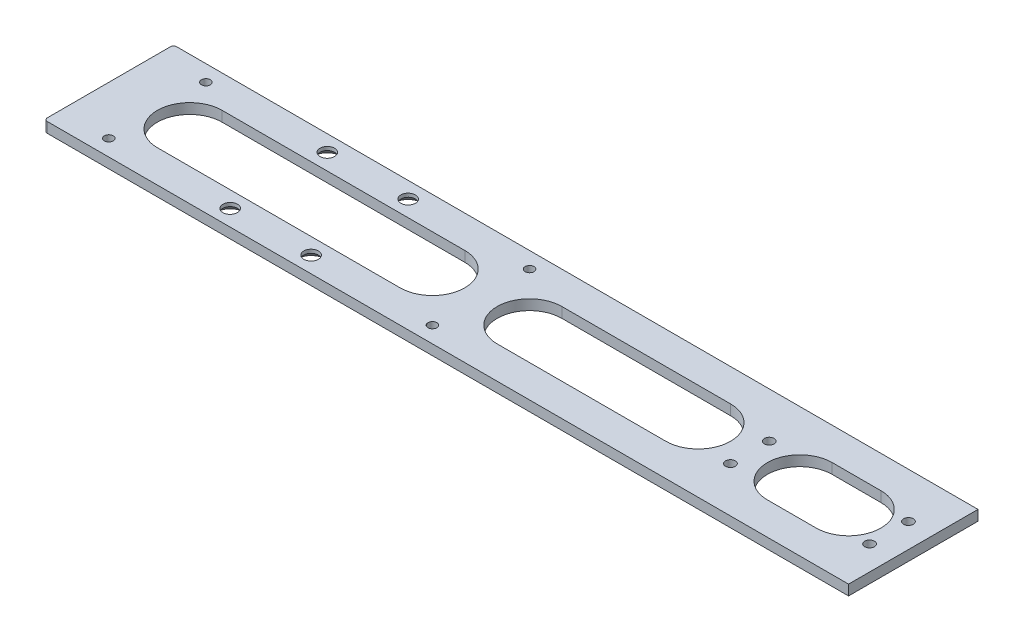
SolidWorks part; units mm, degrees
ref_plane "Alzado" through (0, 0, 0) normal (0, 0, 1) x (1, 0, 0)
ref_plane "Planta" through (0, 0, 0) normal (0, 1, 0) x (1, 0, 0)
ref_plane "Vista lateral" through (0, 0, 0) normal (1, 0, 0) x (0, 0, -1)
sketch "Croquis1" plane through (0, 0, 0) normal (0, 1, 0) x (1, 0, 0)
  line L1 (-149.7778, 34.4444) -> (347.3722, 34.4444)
  line L2 (-149.7778, 34.4444) -> (-149.7778, -45.5556)
  line L3 (-149.7778, -45.5556) -> (347.3722, -45.5556)
  line L4 (347.3722, 34.4444) -> (347.3722, -45.5556)
  dimension "k" = 497.15
  dimension "D2" = 80
base flange "Brida base1" sketch "Croquis1" thickness 6.35 reverse thickness direction no parameters "D1"=10
fillet "Redondeo1" radius 2 2 edges at (-149.7778, -3.175, -34.4444) (-149.7778, -3.175, 45.5556)
hole_wizard "Taladro de margen para M51" positions "Croquis7" profile "Croquis6" hole size "M5" standard "Ansi Metric" end condition through all
sketch "Croquis7" plane through (0, 0, 0) normal (0, 1, 0) x (1, 0, 0)
  line L0 (-149.7778, 32.4444) -> (-149.7778, -43.5556) construction
  line L11 (-149.7778, -5.5556) -> (347.3722, -5.5556) construction
  line L12 (347.3722, -45.5556) -> (347.3722, 34.4444) construction
  point P0 (-119.7778, 24.4444)
  point P2 (-119.7778, -35.5556)
  point P4 (80.2222, -35.5556)
  point P45 (80.2222, 24.4444)
  dimension "D1" = 30
  dimension "D2" = 30
  dimension "D3" = 60
sketch "Croquis6" plane through (-119.7778, 0, -24.4444) normal (1, 0, 0) x (0, 0, 1)
  line L0 (0, 0) -> (0, 6.35)
  line L1 (0, 6.35) -> (2.75, 6.35)
  line L2 (2.75, 6.35) -> (2.75, 0)
  line L5 (2.75, 0) -> (0, 0)
  line L11 (0, -6.35) -> (0, 107.95) construction
  dimension "Diámetro de taladro hasta el siguiente" = 5.5
  dimension "Profundidad de taladro hasta el siguiente" = 6.35
sketch "Croquis8" plane through (0, 0, 0) normal (0, 1, 0) x (1, 0, 0)
  line L0 (-149.7778, -5.5556) -> (347.3722, -5.5556) construction
  line L1 (-149.7778, 32.4444) -> (-149.7778, -43.5556) construction
  line L2 (347.3722, -45.5556) -> (347.3722, 34.4444) construction
  line L3 (99.7972, 34.4444) -> (99.7972, -45.5556) construction
  line L5 (-147.7778, -45.5556) -> (347.3722, -45.5556) construction
  line L6 (347.3722, 34.4444) -> (-147.7778, 34.4444) construction
sketch "Croquis9" plane through (0, -6.35, 0) normal (0, -1, 0) x (-1, 0, 0)
  line L0 (-347.3722, -5.5556) -> (149.7778, -5.5556) construction
  line L1 (-347.3722, -45.5556) -> (-347.3722, 34.4444) construction
  line L2 (149.7778, 32.4444) -> (149.7778, -43.5556) construction
  line L3 (-307.3722, -5.5556) -> (-277.2348, -5.5556) construction
  line L4 (-307.3722, 14.4444) -> (-277.2348, 14.4444)
  line L5 (-307.3722, -25.5556) -> (-277.2348, -25.5556)
  line L6 (-50.2222, -5.5556) -> (99.7778, -5.5556) construction
  line L7 (-50.2222, 14.4444) -> (99.7778, 14.4444)
  line L8 (-50.2222, -25.5556) -> (99.7778, -25.5556)
  line L9 (-214.4819, -5.5556) -> (-110.2222, -5.5556) construction
  line L10 (-214.4819, 14.4444) -> (-110.2222, 14.4444)
  line L11 (-214.4819, -25.5556) -> (-110.2222, -25.5556)
  arc A0 (-307.3722, 14.4444) -> (-307.3722, -25.5556) centre (-307.3722, -5.5556) ccw
  arc A1 (-277.2348, -25.5556) -> (-277.2348, 14.4444) centre (-277.2348, -5.5556) ccw
  arc A2 (-50.2222, 14.4444) -> (-50.2222, -25.5556) centre (-50.2222, -5.5556) ccw
  arc A3 (99.7778, -25.5556) -> (99.7778, 14.4444) centre (99.7778, -5.5556) ccw
  circle A4 centre (-80.2222, 24.4444) radius 2.75 construction
  arc A5 (-214.4819, 14.4444) -> (-214.4819, -25.5556) centre (-214.4819, -5.5556) ccw
  arc A6 (-110.2222, -25.5556) -> (-110.2222, 14.4444) centre (-110.2222, -5.5556) ccw
  point P8 (-292.3035, -5.5556)
  point P13 (24.7778, -5.5556)
  point P24 (-162.3521, -5.5556)
  dimension "D1" = 20
  dimension "D2" = 20
  dimension "D4" = 20
  dimension "D5" = 30
  dimension "D6" = 50
  dimension "D3" = 40
  dimension "D7" = 30
extrude "Cortar-Extruir1" cut sketch "Croquis9" against normal blind 10 normal cut yes
sketch "Croquis10" plane through (0, -6.35, 0) normal (0, -1, 0) x (1, 0, 0)
  line L0 (347.3722, 45.5556) -> (347.3722, -34.4444) construction
  line L1 (347.3722, 5.5556) -> (327.3722, 5.5556) construction
  circle A0 centre (332.3722, 17.5556) radius 3
  circle A1 centre (246.3722, 17.5556) radius 3
  circle A2 centre (246.3722, -6.4444) radius 3
  circle A3 centre (332.3722, -6.4444) radius 3
  arc A4 (307.3722, -14.4444) -> (307.3722, 25.5556) centre (307.3722, 5.5556) ccw construction
  dimension "D1" = 6
  dimension "D2" = 15
  dimension "D5" = 24
  dimension "D6" = 12
  dimension "D3" = 2
  dimension "D4" = 2
extrude "Cortar-Extruir2" cut sketch "Croquis10" against normal blind 10 contours A3
sketch "Sketch1" plane through (0, -6.35, 0) normal (0, -1, 0) x (1, 0, 0)
  line L0 (-69.7778, -34.4444) -> (30.2222, -34.4444) construction
  line L1 (-19.7778, -34.4444) -> (-19.7778, 45.5556) construction
  line L2 (50.2222, -14.4444) -> (-99.7778, -14.4444) construction
  line L3 (50.2222, -14.4444) -> (-99.7778, -14.4444)
  line L4 (-149.7778, 43.5556) -> (-149.7778, -32.4444)
  line L5 (-147.7778, -34.4444) -> (347.3722, -34.4444)
  line L6 (347.3722, -34.4444) -> (347.3722, 45.5556)
  line L7 (347.3722, 45.5556) -> (-147.7778, 45.5556)
  line L8 (-149.7778, 43.5556) -> (-149.7778, -32.4444)
  line L9 (-147.7778, -34.4444) -> (347.3722, -34.4444)
  line L10 (347.3722, -34.4444) -> (347.3722, 45.5556) construction
  line L11 (347.3722, 45.5556) -> (-147.7778, 45.5556)
  line L12 (-149.7778, 5.5556) -> (-69.7778, 5.5556) construction
  line L13 (-69.7778, -34.4444) -> (-69.7778, 45.5556) construction
  line L14 (-69.7778, 5.5556) -> (30.2222, 5.5556) construction
  line L15 (30.2222, 5.5556) -> (30.2222, -34.4444) construction
  line L16 (30.2222, 5.5556) -> (30.2222, 45.5556) construction
  line L17 (-99.7778, -14.4444) -> (50.2222, -14.4444) construction
  line L18 (-99.7778, -14.4444) -> (50.2222, -14.4444)
  line L19 (-69.7778, -34.4444) -> (-69.7778, -24.4444) construction
  line L20 (-69.7778, -24.4444) -> (30.2222, -24.4444) construction
  line L21 (-69.7778, -24.4444) -> (-44.7778, -24.4444)
  line L22 (30.2222, -24.4444) -> (5.2222, -24.4444)
  line L23 (-69.7778, -34.4444) -> (-69.7778, -14.4444) construction
  line L24 (-69.7778, -34.4444) -> (30.2222, -34.4444)
  line L25 (-69.7778, -34.4444) -> (-69.7778, 45.5556)
  line L26 (-69.7778, 45.5556) -> (30.2222, 45.5556)
  line L27 (30.2222, -34.4444) -> (30.2222, 45.5556)
  arc A2 (-149.7778, -32.4444) -> (-147.7778, -34.4444) centre (-147.7778, -32.4444) ccw
  arc A3 (-147.7778, 45.5556) -> (-149.7778, 43.5556) centre (-147.7778, 43.5556) ccw
  arc A4 (-149.7778, -32.4444) -> (-147.7778, -34.4444) centre (-147.7778, -32.4444) ccw
  arc A5 (-147.7778, 45.5556) -> (-149.7778, 43.5556) centre (-147.7778, 43.5556) ccw
  circle A6 centre (-44.7778, -24.4444) radius 4.5
  circle A7 centre (5.2222, -24.4444) radius 4.5
  circle A8 centre (5.2222, 35.5556) radius 4.5
  circle A9 centre (-44.7778, 35.5556) radius 4.5
  dimension "D7" = 9
  dimension "D8" = 9
  dimension "D2" = 80
  dimension "D3" = 100
  dimension "D4" = 25
  dimension "D5" = 25
  dimension "D11" = 30
  dimension "D12" = 30
  dimension "D13" = 25
  dimension "D14" = 25
  dimension "D15" = 25
  dimension "D16" = 25
  dimension "D17" = 30
  dimension "D18" = 30
  dimension "D1" = 0
extrude "Cut-Extrude1" cut sketch "Sketch1" against normal up to surface (6.35 mm away) up to face at (332.3722, 0, -3.4444)
hole_wizard "CSK for M8 Oval Head Machine Screw1" positions "3DSketch2" profile "Sketch7" countersink size "M8" standard "ANSI Metric"
sketch3d "3DSketch2"
  line L0 (5.2222, 0, 35.5556) -> (5.2222, -6.35, 35.5556) construction
  line L1 (-44.7778, 0, 35.5556) -> (-44.7778, -6.35, 35.5556) construction
  line L2 (-44.7778, 0, -24.4444) -> (-44.7778, -6.35, -24.4444) construction
  line L3 (5.2222, 0, -24.4444) -> (5.2222, -6.35, -24.4444) construction
  point P0 (5.2222, -6.35, 35.5556)
  point P4 (-44.7778, -6.35, 35.5556)
  point P8 (-44.7778, -6.35, -24.4444)
  point P12 (5.2222, -6.35, -24.4444)
sketch "Sketch7" plane through (5.2222, -6.35, 35.5556) normal (1, 0, 0) x (0, 0, -1)
  line L0 (0, 0) -> (0, 9.0529)
  line L1 (0, 9.0529) -> (4.5, 6.349)
  line L2 (4.5, 6.349) -> (4.5, 4.15)
  line L3 (4.5, 4.15) -> (8.65, 0)
  line L5 (8.65, 0) -> (0, 0)
  line L6 (-4.5, 4.15) -> (-8.65, 0) construction
  line L10 (0, 9.0529) -> (-4.5, 6.349) construction
  line L11 (0, -6.35) -> (0, 107.95) construction
  dimension "Hole Dia." = 9
  dimension "Hole Depth" = 6.349
  dimension "Near C'Sink Dia." = 17.3
  dimension "Near C'Sink Angle" = 90
  dimension "Drill Angle" = 118
sketch "Líneas de pliegue1" [suppressed] plane through (0, 0, 0) normal (0, 1, 0) x (1, 0, 0)
sketch "Cuadro delimitador1" [suppressed] plane through (0, 0, 0) normal (0, 1, 0) x (1, 0, 0)
sheet metal parameters "Chapa metálica1" thickness 6.35 parameters "D1"=10
flat pattern "Chapa desplegada1" [suppressed]
sketch "Líneas de pliegue2" plane through (0, 0, 0) normal (0, 1, 0) x (1, 0, 0)
sketch3d "Cuadro delimitador2" [suppressed]
  line L0 (-149.7778, -85.5554, 0) -> (110.2222, -85.5556, 0) construction
  line L1 (-149.7777, 34.4444, 0) -> (110.2223, 34.4443, 0) construction
  line L2 (-149.7778, -85.5554, 0) -> (-149.7777, 34.4444, 0) construction
  line L3 (110.2222, -85.5556, 0) -> (110.2223, 34.4443, 0) construction
sheet metal parameters "Chapa metálica2" thickness 6.35 parameters "D1"=10
flat pattern "Chapa desplegada1"
sketch "Líneas de pliegue2" plane through (0, 0, 0) normal (0, 1, 0) x (1, 0, 0)
sketch3d "Cuadro delimitador2" [suppressed]
  line L0 (-149.7778, -45.5553, 0) -> (347.3722, -45.5556, 0) construction
  line L1 (-149.7777, 34.4444, 0) -> (347.3723, 34.4442, 0) construction
  line L2 (-149.7778, -45.5553, 0) -> (-149.7777, 34.4444, 0) construction
  line L3 (347.3722, -45.5556, 0) -> (347.3723, 34.4442, 0) construction
sheet metal parameters "Chapa metálica5" thickness 6.35 parameters "D1"=10
flat pattern "Chapa desplegada1" [suppressed]
sketch "Líneas de pliegue2" plane through (0, 0, 0) normal (0, 1, 0) x (1, 0, 0)
sketch3d "Cuadro delimitador2" [suppressed]
  line L0 (-149.7778, -45.5553, 0) -> (347.3722, -45.5556, 0) construction
  line L1 (-149.7777, 34.4444, 0) -> (347.3723, 34.4442, 0) construction
  line L2 (-149.7778, -45.5553, 0) -> (-149.7777, 34.4444, 0) construction
  line L3 (347.3722, -45.5556, 0) -> (347.3723, 34.4442, 0) construction
sketch "Croquis10-1" [suppressed] plane through (0, -3, 0) normal (0, -1, 0) x (1, 0, 0)
  line L0 (347.3722, 45.5556) -> (347.3722, -34.4444) construction
  line L1 (347.3722, 5.5556) -> (327.3722, 5.5556) construction
  circle A0 centre (332.3722, 17.5556) radius 3
  circle A1 centre (246.3722, 17.5556) radius 3
  circle A2 centre (246.3722, -6.4444) radius 3
  circle A3 centre (332.3722, -6.4444) radius 3
  dimension "D1" = 6
  dimension "D2" = 15
  dimension "D5" = 24
  dimension "D6" = 12
  dimension "D3" = 2
  dimension "D4" = 2
sketch "Croquis10-2" [suppressed] plane through (0, -3, 0) normal (0, -1, 0) x (1, 0, 0)
  line L0 (347.3722, 45.5556) -> (347.3722, -34.4444) construction
  line L1 (347.3722, 5.5556) -> (327.3722, 5.5556) construction
  circle A0 centre (332.3722, 17.5556) radius 3
  circle A1 centre (246.3722, 17.5556) radius 3
  circle A2 centre (246.3722, -6.4444) radius 3
  circle A3 centre (332.3722, -6.4444) radius 3
  dimension "D1" = 6
  dimension "D2" = 15
  dimension "D5" = 24
  dimension "D6" = 12
  dimension "D3" = 2
  dimension "D4" = 2
sheet metal parameters "Chapa metálica6" thickness 6.35 parameters "D1"=10
flat pattern "Chapa desplegada1" [suppressed]
sketch "Líneas de pliegue2" plane through (0, 0, 0) normal (0, 1, 0) x (1, 0, 0)
sketch3d "Cuadro delimitador2" [suppressed]
  line L0 (-149.7778, -45.5553, 0) -> (347.3722, -45.5556, 0) construction
  line L1 (-149.7777, 34.4444, 0) -> (347.3723, 34.4442, 0) construction
  line L2 (-149.7778, -45.5553, 0) -> (-149.7777, 34.4444, 0) construction
  line L3 (347.3722, -45.5556, 0) -> (347.3723, 34.4442, 0) construction
sketch "Croquis10-1" plane through (0, -6.35, 0) normal (0, -1, 0) x (1, 0, 0)
  line L0 (347.3722, 45.5556) -> (347.3722, -34.4444) construction
  line L1 (347.3722, 5.5556) -> (327.3722, 5.5556) construction
  circle A0 centre (332.3722, 17.5556) radius 3
  circle A1 centre (246.3722, 17.5556) radius 3
  circle A2 centre (246.3722, -6.4444) radius 3
  circle A3 centre (332.3722, -6.4444) radius 3
  dimension "D1" = 6
  dimension "D2" = 15
  dimension "D5" = 24
  dimension "D6" = 12
  dimension "D3" = 2
  dimension "D4" = 2
sketch "Croquis10-2" [suppressed] plane through (0, -3, 0) normal (0, -1, 0) x (1, 0, 0)
  line L0 (347.3722, 45.5556) -> (347.3722, -34.4444)
  line L1 (347.3722, 5.5556) -> (327.3722, 5.5556) construction
  circle A0 centre (332.3722, 17.5556) radius 3
  circle A1 centre (246.3722, 17.5556) radius 3
  circle A2 centre (246.3722, -6.4444) radius 3
  circle A3 centre (332.3722, -6.4444) radius 3
  dimension "D1" = 6
  dimension "D2" = 15
  dimension "D5" = 24
  dimension "D6" = 12
  dimension "D3" = 2
  dimension "D4" = 2
sketch "Croquis10-3" [suppressed] plane through (0, -3, 0) normal (0, -1, 0) x (1, 0, 0)
  line L0 (347.3722, 45.5556) -> (347.3722, -34.4444) construction
  line L1 (347.3722, 5.5556) -> (327.3722, 5.5556) construction
  circle A0 centre (332.3722, 17.5556) radius 3
  circle A1 centre (246.3722, 17.5556) radius 3
  circle A2 centre (246.3722, -6.4444) radius 3
  circle A3 centre (332.3722, -6.4444) radius 3
  dimension "D1" = 6
  dimension "D2" = 15
  dimension "D5" = 24
  dimension "D6" = 12
  dimension "D3" = 2
  dimension "D4" = 2
sketch "Croquis10-4" plane through (0, -6.35, 0) normal (0, -1, 0) x (1, 0, 0)
  line L0 (347.3722, 45.5556) -> (347.3722, -34.4444) construction
  line L1 (347.3722, 5.5556) -> (327.3722, 5.5556) construction
  circle A0 centre (332.3722, 17.5556) radius 3
  circle A1 centre (246.3722, 17.5556) radius 3
  circle A2 centre (246.3722, -6.4444) radius 3
  circle A3 centre (332.3722, -6.4444) radius 3
  dimension "D1" = 6
  dimension "D2" = 15
  dimension "D5" = 24
  dimension "D6" = 12
  dimension "D3" = 2
  dimension "D4" = 2
sheet metal parameters "Sheet-Metal8" thickness 6.35 parameters "D1"=10
flat pattern "Chapa desplegada1" [suppressed]
sketch "Líneas de pliegue2" plane through (0, 0, 0) normal (0, 1, 0) x (1, 0, 0)
sketch3d "Cuadro delimitador2" [suppressed]
  line L0 (-149.7778, -45.5553, 0) -> (347.3722, -45.5556, 0) construction
  line L1 (-149.7777, 34.4444, 0) -> (347.3723, 34.4442, 0) construction
  line L2 (-149.7778, -45.5553, 0) -> (-149.7777, 34.4444, 0) construction
  line L3 (347.3722, -45.5556, 0) -> (347.3723, 34.4442, 0) construction
sketch "Croquis10-1" plane through (0, -6.35, 0) normal (0, -1, 0) x (1, 0, 0)
  line L0 (347.3722, 45.5556) -> (347.3722, -34.4444) construction
  line L1 (347.3722, 5.5556) -> (327.3722, 5.5556) construction
  circle A0 centre (332.3722, 17.5556) radius 3
  circle A1 centre (246.3722, 17.5556) radius 3
  circle A2 centre (246.3722, -6.4444) radius 3
  circle A3 centre (332.3722, -6.4444) radius 3
  dimension "D1" = 6
  dimension "D2" = 15
  dimension "D5" = 24
  dimension "D6" = 12
  dimension "D3" = 2
  dimension "D4" = 2
sketch "Croquis10-2" [suppressed] plane through (0, -3, 0) normal (0, -1, 0) x (1, 0, 0)
  line L0 (347.3722, 45.5556) -> (347.3722, -34.4444)
  line L1 (347.3722, 5.5556) -> (327.3722, 5.5556) construction
  circle A0 centre (332.3722, 17.5556) radius 3
  circle A1 centre (246.3722, 17.5556) radius 3
  circle A2 centre (246.3722, -6.4444) radius 3
  circle A3 centre (332.3722, -6.4444) radius 3
  dimension "D1" = 6
  dimension "D2" = 15
  dimension "D5" = 24
  dimension "D6" = 12
  dimension "D3" = 2
  dimension "D4" = 2
sketch "Croquis10-3" [suppressed] plane through (0, -3, 0) normal (0, -1, 0) x (1, 0, 0)
  line L0 (347.3722, 45.5556) -> (347.3722, -34.4444)
  line L1 (347.3722, 5.5556) -> (327.3722, 5.5556) construction
  circle A0 centre (332.3722, 17.5556) radius 3
  circle A1 centre (246.3722, 17.5556) radius 3
  circle A2 centre (246.3722, -6.4444) radius 3
  circle A3 centre (332.3722, -6.4444) radius 3
  dimension "D1" = 6
  dimension "D2" = 15
  dimension "D5" = 24
  dimension "D6" = 12
  dimension "D3" = 2
  dimension "D4" = 2
sketch "Croquis10-4" plane through (0, -6.35, 0) normal (0, -1, 0) x (1, 0, 0)
  line L0 (347.3722, 45.5556) -> (347.3722, -34.4444)
  line L1 (347.3722, 5.5556) -> (327.3722, 5.5556) construction
  circle A0 centre (332.3722, 17.5556) radius 3
  circle A1 centre (246.3722, 17.5556) radius 3
  circle A2 centre (246.3722, -6.4444) radius 3
  circle A3 centre (332.3722, -6.4444) radius 3
  dimension "D1" = 6
  dimension "D2" = 15
  dimension "D5" = 24
  dimension "D6" = 12
  dimension "D3" = 2
  dimension "D4" = 2
sketch "Croquis10-5" plane through (0, -6.35, 0) normal (0, -1, 0) x (1, 0, 0)
  line L0 (347.3722, 45.5556) -> (347.3722, -34.4444) construction
  line L1 (347.3722, 5.5556) -> (327.3722, 5.5556) construction
  circle A0 centre (332.3722, 17.5556) radius 3
  circle A1 centre (246.3722, 17.5556) radius 3
  circle A2 centre (246.3722, -6.4444) radius 3
  circle A3 centre (332.3722, -6.4444) radius 3
  dimension "D1" = 6
  dimension "D2" = 15
  dimension "D5" = 24
  dimension "D6" = 12
  dimension "D3" = 2
  dimension "D4" = 2
sheet metal parameters "Sheet-Metal10" thickness 6.35 parameters "D1"=10
flat pattern "Chapa desplegada1" [suppressed]
sketch "Líneas de pliegue2" plane through (0, 0, 0) normal (0, 1, 0) x (1, 0, 0)
sketch3d "Cuadro delimitador2" [suppressed]
  line L0 (-149.7778, -45.5553, 0) -> (347.3722, -45.5556, 0) construction
  line L1 (-149.7777, 34.4444, 0) -> (347.3723, 34.4442, 0) construction
  line L2 (-149.7778, -45.5553, 0) -> (-149.7777, 34.4444, 0) construction
  line L3 (347.3722, -45.5556, 0) -> (347.3723, 34.4442, 0) construction
sketch "Croquis10-1" plane through (0, -6.35, 0) normal (0, -1, 0) x (1, 0, 0)
  line L0 (347.3722, 45.5556) -> (347.3722, -34.4444) construction
  line L1 (347.3722, 5.5556) -> (327.3722, 5.5556) construction
  circle A0 centre (332.3722, 17.5556) radius 3
  circle A1 centre (246.3722, 17.5556) radius 3
  circle A2 centre (246.3722, -6.4444) radius 3
  circle A3 centre (332.3722, -6.4444) radius 3
  dimension "D1" = 6
  dimension "D2" = 15
  dimension "D5" = 24
  dimension "D6" = 12
  dimension "D3" = 2
  dimension "D4" = 2
sketch "Croquis10-2" [suppressed] plane through (0, -3, 0) normal (0, -1, 0) x (1, 0, 0)
  line L0 (347.3722, 45.5556) -> (347.3722, -34.4444)
  line L1 (347.3722, 5.5556) -> (327.3722, 5.5556) construction
  circle A0 centre (332.3722, 17.5556) radius 3
  circle A1 centre (246.3722, 17.5556) radius 3
  circle A2 centre (246.3722, -6.4444) radius 3
  circle A3 centre (332.3722, -6.4444) radius 3
  dimension "D1" = 6
  dimension "D2" = 15
  dimension "D5" = 24
  dimension "D6" = 12
  dimension "D3" = 2
  dimension "D4" = 2
sketch "Croquis10-3" [suppressed] plane through (0, -3, 0) normal (0, -1, 0) x (1, 0, 0)
  line L0 (347.3722, 45.5556) -> (347.3722, -34.4444)
  line L1 (347.3722, 5.5556) -> (327.3722, 5.5556) construction
  circle A0 centre (332.3722, 17.5556) radius 3
  circle A1 centre (246.3722, 17.5556) radius 3
  circle A2 centre (246.3722, -6.4444) radius 3
  circle A3 centre (332.3722, -6.4444) radius 3
  dimension "D1" = 6
  dimension "D2" = 15
  dimension "D5" = 24
  dimension "D6" = 12
  dimension "D3" = 2
  dimension "D4" = 2
sketch "Croquis10-4" plane through (0, -6.35, 0) normal (0, -1, 0) x (1, 0, 0)
  line L0 (347.3722, 45.5556) -> (347.3722, -34.4444)
  line L1 (347.3722, 5.5556) -> (327.3722, 5.5556) construction
  circle A0 centre (332.3722, 17.5556) radius 3
  circle A1 centre (246.3722, 17.5556) radius 3
  circle A2 centre (246.3722, -6.4444) radius 3
  circle A3 centre (332.3722, -6.4444) radius 3
  dimension "D1" = 6
  dimension "D2" = 15
  dimension "D5" = 24
  dimension "D6" = 12
  dimension "D3" = 2
  dimension "D4" = 2
sketch "Croquis10-5" plane through (0, -6.35, 0) normal (0, -1, 0) x (1, 0, 0)
  line L0 (347.3722, 45.5556) -> (347.3722, -34.4444)
  line L1 (347.3722, 5.5556) -> (327.3722, 5.5556) construction
  circle A0 centre (332.3722, 17.5556) radius 3
  circle A1 centre (246.3722, 17.5556) radius 3
  circle A2 centre (246.3722, -6.4444) radius 3
  circle A3 centre (332.3722, -6.4444) radius 3
  dimension "D1" = 6
  dimension "D2" = 15
  dimension "D5" = 24
  dimension "D6" = 12
  dimension "D3" = 2
  dimension "D4" = 2
sketch "Croquis10-7" plane through (0, -6.35, 0) normal (0, -1, 0) x (1, 0, 0)
  line L0 (347.3722, 45.5556) -> (347.3722, -34.4444) construction
  line L1 (347.3722, 5.5556) -> (327.3722, 5.5556) construction
  circle A0 centre (332.3722, 17.5556) radius 3
  circle A1 centre (246.3722, 17.5556) radius 3
  circle A2 centre (246.3722, -6.4444) radius 3
  circle A3 centre (332.3722, -6.4444) radius 3
  dimension "D1" = 6
  dimension "D2" = 15
  dimension "D5" = 24
  dimension "D6" = 12
  dimension "D3" = 2
  dimension "D4" = 2
sketch "Croquis10-8" plane through (0, -6.35, 0) normal (0, -1, 0) x (1, 0, 0)
  line L0 (347.3722, 45.5556) -> (347.3722, -34.4444) construction
  line L1 (347.3722, 5.5556) -> (327.3722, 5.5556) construction
  circle A0 centre (332.3722, 17.5556) radius 3
  circle A1 centre (246.3722, 17.5556) radius 3
  circle A2 centre (246.3722, -6.4444) radius 3
  circle A3 centre (332.3722, -6.4444) radius 3
  dimension "D1" = 6
  dimension "D2" = 15
  dimension "D5" = 24
  dimension "D6" = 12
  dimension "D3" = 2
  dimension "D4" = 2
sketch "Croquis10-9" plane through (0, -6.35, 0) normal (0, -1, 0) x (1, 0, 0)
  line L0 (347.3722, 45.5556) -> (347.3722, -34.4444) construction
  line L1 (347.3722, 5.5556) -> (327.3722, 5.5556) construction
  circle A0 centre (332.3722, 17.5556) radius 3
  circle A1 centre (246.3722, 17.5556) radius 3
  circle A2 centre (246.3722, -6.4444) radius 3
  circle A3 centre (332.3722, -6.4444) radius 3
  dimension "D1" = 6
  dimension "D2" = 15
  dimension "D5" = 24
  dimension "D6" = 12
  dimension "D3" = 2
  dimension "D4" = 2
